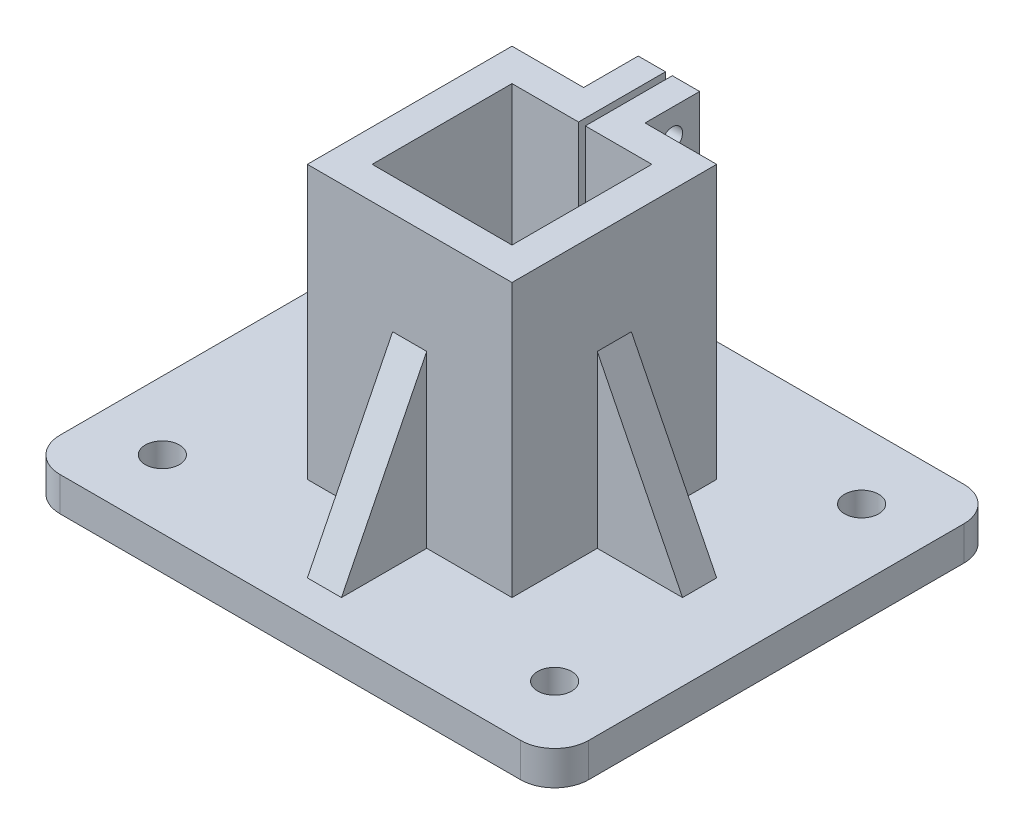
SolidWorks part; units mm, degrees
ref_plane "Front Plane" through (0, 0, 0) normal (0, 0, 1) x (1, 0, 0)
ref_plane "Top Plane" through (0, 0, 0) normal (0, 1, 0) x (1, 0, 0)
ref_plane "Right Plane" through (0, 0, 0) normal (1, 0, 0) x (0, 0, -1)
sketch "Sketch1" plane through (0, 0, 0) normal (0, 1, 0) x (1, 0, 0)
  line L0 (-38.75, 32.5) -> (38.75, -32.5) construction
  line L1 (-38.75, 32.5) -> (38.75, 32.5)
  line L2 (-38.75, 32.5) -> (-38.75, -32.5)
  line L3 (-38.75, -32.5) -> (38.75, -32.5)
  line L4 (38.75, 32.5) -> (38.75, -32.5)
  dimension "D1" = 77.5
  dimension "D2" = 65
extrude "Boss-Extrude1" add sketch "Sketch1" along normal blind 5
sketch "Sketch2" plane through (0, 5, 0) normal (0, 1, 0) x (1, 0, 0)
  line L0 (-28.75, 22.5) -> (28.75, -22.5) construction
  line L1 (-28.75, 22.5) -> (28.75, 22.5) construction
  line L2 (-28.75, 22.5) -> (-28.75, -22.5) construction
  line L3 (-28.75, -22.5) -> (28.75, -22.5) construction
  line L4 (28.75, 22.5) -> (28.75, -22.5) construction
  point P5 (-28.75, 22.5)
  point P7 (28.75, 22.5)
  point P8 (28.75, -22.5)
  point P9 (-28.75, -22.5)
  dimension "D1" = 57.5
  dimension "D2" = 45
hole_wizard "Ø5.0 (5) Diameter Hole1" positions "3DSketch1" profile "Sketch3" hole size "Ø5.0" standard "ANSI Metric" end condition up to next
sketch3d "3DSketch1"
  point P0 (-28.75, 5, -22.5)
  point P3 (28.75, 5, -22.5)
  point P6 (28.75, 5, 22.5)
  point P13 (-28.75, 5, 22.5)
sketch "Sketch3" plane through (-28.75, 5, -22.5) normal (1, 0, 0) x (0, 0, 1)
  line L0 (0, 0) -> (0, 5)
  line L1 (0, 5) -> (2.5, 5)
  line L2 (2.5, 5) -> (2.5, 0)
  line L5 (2.5, 0) -> (0, 0)
  line L11 (0, -6.35) -> (0, 107.95) construction
  dimension "Thru Hole Dia." = 5
  dimension "Thru Hole Depth" = 5
sketch "Sketch4" plane through (0, 5, 0) normal (0, 1, 0) x (1, 0, 0)
  line L0 (-15, 15) -> (15, -15) construction
  line L1 (-15, 15) -> (15, 15)
  line L2 (-15, 15) -> (-15, -15)
  line L3 (-15, -15) -> (15, -15)
  line L4 (15, 15) -> (15, -15)
  dimension "D1" = 30
extrude "Boss-Extrude2" add sketch "Sketch4" along normal blind 40
sketch "Sketch5" plane through (0, 45, 0) normal (0, 1, 0) x (1, 0, 0)
  line L0 (-10.25, 10.25) -> (10.25, -10.25) construction
  line L1 (-10.25, 10.25) -> (10.25, 10.25)
  line L2 (-10.25, 10.25) -> (-10.25, -10.25)
  line L3 (-10.25, -10.25) -> (10.25, -10.25)
  line L4 (10.25, 10.25) -> (10.25, -10.25)
  dimension "D1" = 20.5
extrude "Cut-Extrude1" cut sketch "Sketch5" against normal up to next
sketch "Sketch7" plane through (0, 0, 0) normal (1, 0, 0) x (0, 0, -1)
  line L0 (-15, 30) -> (-27.5, 5)
  line L1 (-15, 45) -> (-15, 5) construction
  line L2 (-32.5, 5) -> (32.5, 5) construction
  line L3 (-27.5, 5) -> (-15, 5)
  line L4 (-15, 5) -> (-15, 30)
  dimension "D1" = 25
  dimension "D2" = 12.5
extrude "Boss-Extrude3" add sketch "Sketch7" along normal blind 2.5 and the other way blind 2.5
ref_axis "Axis1" through (0, -2.25, 0) along (0, 1, 0)
pattern_circular "CirPattern1" count 2 every 90 about axis through (0, -2.25, 0) along (0, 1, 0) of "Boss-Extrude3"
pattern_circular "CirPattern2" count 2 over 90 about axis through (0, -2.25, 0) along (0, 1, 0) of "Boss-Extrude3" reverse direction yes
sketch "Sketch11" plane through (0, 0, -15) normal (0, 0, -1) x (-1, 0, 0)
  line L0 (-15, 45) -> (15, 45) construction
  line L1 (-0.5, 45) -> (0.5, 45)
  line L2 (-0.5, 45) -> (-0.5, 5)
  line L3 (-0.5, 5) -> (0.5, 5)
  line L4 (0.5, 45) -> (0.5, 5)
  line L5 (-38.75, 5) -> (38.75, 5) construction
  point P8 (0, 5)
  dimension "D1" = 1
extrude "Cut-Extrude4" cut sketch "Sketch11" against normal up to next
sketch "Sketch12" plane through (0, 0, -15) normal (0, 0, -1) x (-1, 0, 0)
  line L1 (-0.5, 45) -> (-4.5, 45)
  line L2 (-0.5, 45) -> (-0.5, 37)
  line L3 (-0.5, 37) -> (-4.5, 37)
  line L4 (-4.5, 45) -> (-4.5, 37)
  dimension "D1" = 4
  dimension "D2" = 8
extrude "Boss-Extrude5" add sketch "Sketch12" along normal blind 8
fillet "Fillet3" radius 8 1 edges at (2.5, 37, -15)
mirror "Mirror2" about plane through (0, 0, 0) normal (1, 0, 0) of "Fillet3", "Boss-Extrude5"
sketch "Sketch13" plane through (-4.5, 0, 0) normal (-1, 0, 0) x (0, 0, 1)
  line L0 (-23, 37) -> (-15, 45) construction
  circle A0 centre (-19, 41) radius 2.15
  dimension "D1" = 4.3
extrude "Cut-Extrude5" cut sketch "Sketch13" against normal up to next
sketch "Sketch14" plane through (-4.5, 0, 0) normal (-1, 0, 0) x (0, 0, 1)
  circle A0 centre (-19, 41) radius 2.75
  dimension "D1" = 5.5
extrude "Cut-Extrude6" cut sketch "Sketch14" against normal blind 1.5
sketch "Sketch15" plane through (4.5, 0, 0) normal (1, 0, 0) x (0, 0, -1)
  circle A0 centre (19, 41) radius 1.5
  dimension "D1" = 3
extrude "Cut-Extrude7" cut sketch "Sketch15" against normal up to next
fillet "Fillet1" radius 5 4 edges at (38.75, 2.5, -32.5) (-38.75, 2.5, -32.5) (38.75, 2.5, 32.5) (-38.75, 2.5, 32.5)
